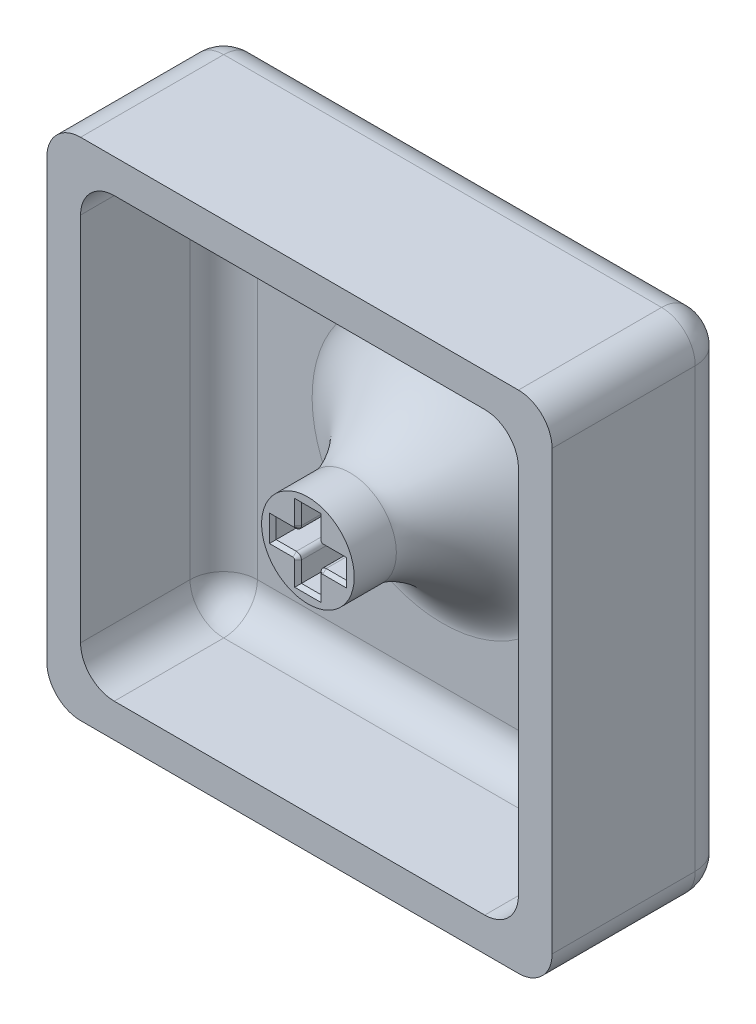
SolidWorks part; units mm, degrees
other "标注1"
sketch "草图2" plane through (15, -15, 10) normal (0.3933, -0.7926, 0.466) x (0.9059, 0.4207, -0.0491)
ref_plane "前视基准面" through (0, 0, 0) normal (0, 0, 1) x (1, 0, 0)
ref_plane "上视基准面" through (0, 0, 0) normal (0, 1, 0) x (1, 0, 0)
ref_plane "右视基准面" through (0, 0, 0) normal (1, 0, 0) x (0, 0, -1)
sketch "草图1" plane through (0, 0, 0) normal (0, 0, 1) x (1, 0, 0)
  line L0 (-13, 15) -> (13, 15)
  line L1 (-11, 13) -> (11, 13)
  line L2 (-13, 11) -> (-13, -11)
  line L3 (-11, -13) -> (11, -13)
  line L4 (13, 11) -> (13, -11)
  line L5 (0, -13) -> (0, 13) construction
  line L6 (-13, 0) -> (13, 0) construction
  line L7 (15, 13) -> (15, -13)
  line L8 (-13, -15) -> (13, -15)
  line L9 (-15, 13) -> (-15, -13)
  line L10 (-13, -13) -> (13, -13) construction
  line L11 (-2.085, 0.585) -> (2.085, 0.585)
  line L12 (-2.085, 0.585) -> (-2.085, -0.585)
  line L13 (-2.085, -0.585) -> (2.085, -0.585)
  line L14 (2.085, 0.585) -> (2.085, -0.585)
  line L15 (0, -0.585) -> (0, 0.585) construction
  line L16 (-2.085, 0) -> (2.085, 0) construction
  line L17 (-0.585, 2.085) -> (0.585, 2.085)
  line L18 (-0.585, 2.085) -> (-0.585, -2.085)
  line L19 (-0.585, -2.085) -> (0.585, -2.085)
  line L20 (0.585, 2.085) -> (0.585, -2.085)
  line L21 (0, -2.085) -> (0, 2.085) construction
  line L22 (-0.585, 0) -> (0.585, 0) construction
  line L23 (13, 13) -> (13, -13) construction
  line L24 (-13, 13) -> (13, 13) construction
  line L25 (-13, 13) -> (-13, -13) construction
  line L26 (-15, 15) -> (-15, -15) construction
  line L27 (-15, -15) -> (15, -15) construction
  line L28 (15, 15) -> (15, -15) construction
  line L29 (-15, 15) -> (15, 15) construction
  line L36 (-13, 0) -> (-2.5, 0) construction
  circle A0 centre (0, 0) radius 2.75
  arc A1 (11, -13) -> (13, -11) centre (11, -11) ccw
  arc A2 (13, 11) -> (11, 13) centre (11, 11) ccw
  arc A3 (-13, 11) -> (-11, 13) centre (-11, 11) cw
  arc A4 (-13, -11) -> (-11, -13) centre (-11, -11) ccw
  arc A5 (-15, -13) -> (-13, -15) centre (-13, -13) ccw
  arc A6 (13, -15) -> (15, -13) centre (13, -13) ccw
  arc A7 (15, 13) -> (13, 15) centre (13, 13) ccw
  arc A8 (-15, 13) -> (-13, 15) centre (-13, 13) cw
  point P0 (0, 0)
  point P19 (13, -13)
  point P66 (0.0162, 0.0162)
  dimension "D4" = 5.5
  dimension "D9" = 2
  dimension "D1" = 30
  dimension "D2" = 30
  dimension "D5" = 4.17
  dimension "D6" = 1.17
  dimension "D7" = 4.17
  dimension "D8" = 1.17
  dimension "D3" = 2
extrude "凸台-拉伸1" add sketch "草图1" along normal blind 8.5 contours A8 L9 A5 L8 A6 L7 A7 L0 A4 L2 A3 L1 A2 L4 A1 L3 region at (0, 14.5757, 0)
extrude "凸台-拉伸2" add sketch "草图1<6>" along normal blind 8 separate body contours A0 L17 L20 L11 L14 L13 L19 L18 L12 region at (-2.6722, 0, 0)
sketch "草图1<6>" plane through (0, 0, 0) normal (0, 0, 1) x (1, 0, 0) same geometry as "草图1"
extrude "凸台-拉伸3" add sketch "草图1<7>" against normal blind 2 contours L8 A6 L7 A7 L0 A8 L9 A5
sketch "草图1<7>" plane through (0, 0, 0) normal (0, 0, 1) x (1, 0, 0) same geometry as "草图1"
fillet "圆角4" radius 0.3 4 edges at (-0.585, 0.585, 4) (0.585, 0.585, 4) (-0.585, -0.585, 4) (0.585, -0.585, 4)
fillet "圆角1" radius 2 8 edges at (-14.4142, 14.4142, -2) (-15, 0, -2) (-14.4142, -14.4142, -2) (0, -15, -2) (14.4142, -14.4142, -2) (15, 0, -2) (14.4142, 14.4142, -2) (0, 15, -2)
chamfer "倒角1" distance 0.2 angle 45 16 edges at (-0.585, 1.485, 8) (-1.485, 0.585, 8) (-2.085, 0, 8) (-1.485, -0.585, 8) (-0.585, -1.485, 8) (0, -2.085, 8) (0.585, -1.485, 8) (1.485, -0.585, 8) (2.085, 0, 8) (1.485, 0.585, 8) (0.585, 1.485, 8) (0, 2.085, 8) (-0.6729, -0.6729, 8) (0.6729, -0.6729, 8) (0.6729, 0.6729, 8) (-0.6729, 0.6729, 8)
fillet "圆角2" radius 2 8 edges at (-12.4142, -12.4142, 0) (-13, 0, 0) (-12.4142, 12.4142, 0) (0, 13, 0) (12.4142, 12.4142, 0) (13, 0, 0) (12.4142, -12.4142, 0) (0, -13, 0)
fillet "圆角3" radius 5 1 edges at (2.75, 0, 0) second distance 5.5 conic rho 0.25 first distance on face at (0, 0, 0)
sketch "草图3" plane through (0, 0, 0) normal (0, 0, 1) x (1, 0, 0)
  line L12 (0.585, 0.885) -> (0.585, 2.085)
  line L13 (0.585, 2.085) -> (-0.585, 2.085)
  line L14 (-0.585, 2.085) -> (-0.585, 0.885)
  line L15 (-0.885, 0.585) -> (-2.085, 0.585)
  line L16 (-2.085, 0.585) -> (-2.085, -0.585)
  line L17 (-2.085, -0.585) -> (-0.885, -0.585)
  line L18 (-0.585, -0.885) -> (-0.585, -2.085)
  line L19 (-0.585, -2.085) -> (0.585, -2.085)
  line L20 (0.585, -2.085) -> (0.585, -0.885)
  line L21 (0.885, -0.585) -> (2.085, -0.585)
  line L22 (2.085, -0.585) -> (2.085, 0.585)
  line L23 (2.085, 0.585) -> (0.885, 0.585)
  line L24 (0.585, 0.885) -> (0.585, 2.085)
  line L25 (0.585, 2.085) -> (-0.585, 2.085)
  line L26 (-0.585, 2.085) -> (-0.585, 0.885)
  line L27 (-0.885, 0.585) -> (-2.085, 0.585)
  line L28 (-2.085, 0.585) -> (-2.085, -0.585)
  line L29 (-2.085, -0.585) -> (-0.885, -0.585)
  line L30 (-0.585, -0.885) -> (-0.585, -2.085)
  line L31 (-0.585, -2.085) -> (0.585, -2.085)
  line L32 (0.585, -2.085) -> (0.585, -0.885)
  line L33 (0.885, -0.585) -> (2.085, -0.585)
  line L34 (2.085, -0.585) -> (2.085, 0.585)
  line L35 (2.085, 0.585) -> (0.885, 0.585)
  arc A4 (-0.885, 0.585) -> (-0.585, 0.885) centre (-0.885, 0.885) ccw
  arc A5 (-0.585, -0.885) -> (-0.885, -0.585) centre (-0.885, -0.885) ccw
  arc A6 (0.885, -0.585) -> (0.585, -0.885) centre (0.885, -0.885) ccw
  arc A7 (0.585, 0.885) -> (0.885, 0.585) centre (0.885, 0.885) ccw
  arc A8 (-0.885, 0.585) -> (-0.585, 0.885) centre (-0.885, 0.885) ccw
  arc A9 (-0.585, -0.885) -> (-0.885, -0.585) centre (-0.885, -0.885) ccw
  arc A10 (0.885, -0.585) -> (0.585, -0.885) centre (0.885, -0.885) ccw
  arc A11 (0.585, 0.885) -> (0.885, 0.585) centre (0.885, 0.885) ccw
  dimension "D1" = 0
extrude "凸台-拉伸4" add sketch "草图3" along normal blind 4
